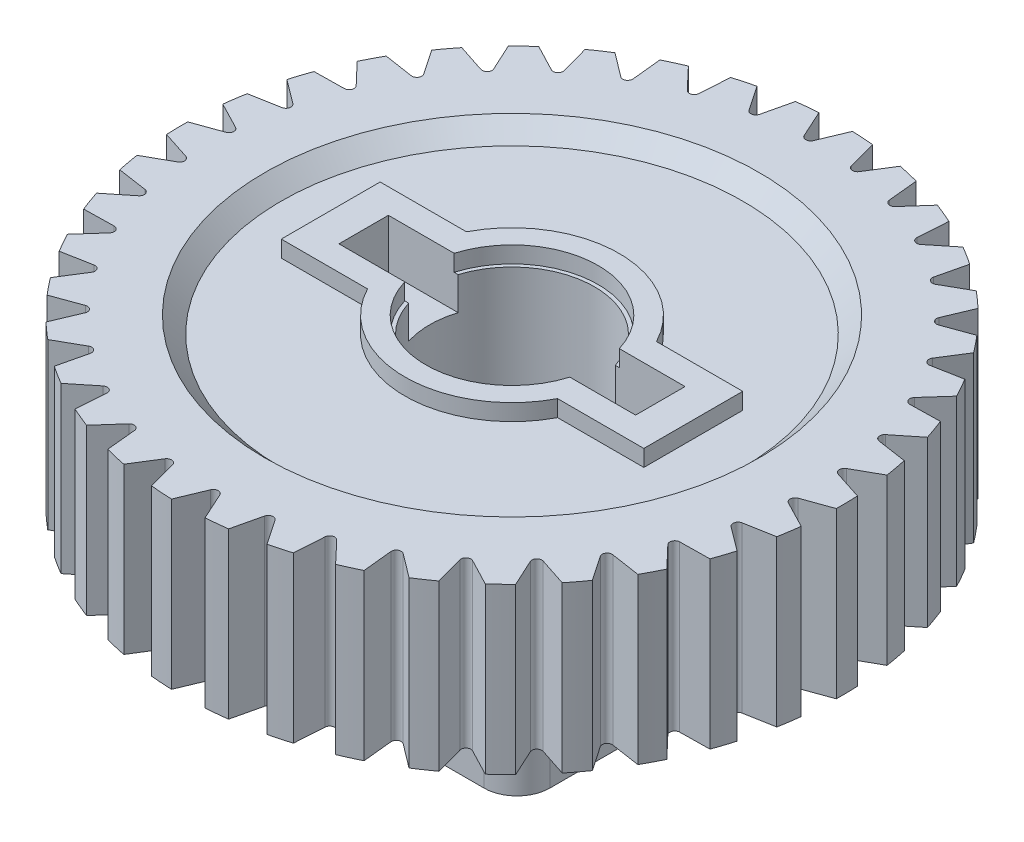
SolidWorks part; units mm, degrees
material "PBT General Purpose"
ref_plane "Front Plane" through (0, 0, 0) normal (0, 0, 1) x (1, 0, 0)
ref_plane "Top Plane" through (0, 0, 0) normal (0, 1, 0) x (1, 0, 0)
ref_plane "Right Plane" through (0, 0, 0) normal (1, 0, 0) x (0, 0, -1)
sketch "Sketch1" plane through (0, 0, 0) normal (0, 1, 0) x (1, 0, 0)
  line L0 (0, 0) -> (12.8047, 15.3636) construction
  line L1 (0, 0) -> (11.2062, 16.5657) construction
  line L2 (11.2062, 16.5657) -> (10.6283, 14.1334)
  line L3 (10.6283, 14.1334) -> (12.8047, 15.3636)
  circle A0 centre (0, 0) radius 20
  dimension "D1" = 40
  dimension "D2" = 2
  dimension "D3" = 2.5
extrude "Boss-Extrude1" add sketch "Sketch1" along normal blind 10 contours L2 A0 L3 region at (-0.0214, 0, 0.0285)
fillet "Fillet1" radius 0.3 1 edges at (10.6283, 5, -14.1334)
ref_axis "Axis1" through (0, 10, 0) along (0, -1, 0)
pattern_circular "CirPattern1" count 38 over 360 about axis through (0, 10, 0) along (0, -1, 0) of face at (12.0157, 5, -14.9176) of face at (10.9529, 5, -14.565) of face at (10.9967, 5, -15.6839)
sketch "Sketch2" plane through (0, 10, 0) normal (0, 1, 0) x (1, 0, 0)
  circle A0 centre (0, 0) radius 5
  dimension "D1" = 10
extrude "Cut-Extrude1" cut sketch "Sketch2" against normal blind 10
sketch "Sketch3" plane through (0, 10, 0) normal (0, 1, 0) x (1, 0, 0)
  circle A0 centre (0, 0) radius 14
  dimension "D1" = 28
extrude "Cut-Extrude2" cut sketch "Sketch3" against normal blind 1
chamfer "Chamfer1" distance 1 angle 45 1 edges at (0, 10, 14)
sketch "Sketch4" plane through (0, 9, 0) normal (0, 1, 0) x (1, 0, 0)
  line L1 (-11, 3) -> (11, 3)
  line L2 (-11, 3) -> (-11, -3)
  line L3 (-11, -3) -> (11, -3)
  line L4 (11, 3) -> (11, -3)
  line L5 (-11, 3) -> (11, -3) construction
  line L6 (-11, -3) -> (11, 3) construction
  line L7 (-9, 1.5) -> (9, 1.5)
  line L8 (-9, 1.5) -> (-9, -1.5)
  line L9 (-9, -1.5) -> (9, -1.5)
  line L10 (9, 1.5) -> (9, -1.5)
  line L11 (-9, 1.5) -> (9, -1.5) construction
  line L12 (-9, -1.5) -> (9, 1.5) construction
  circle A0 centre (0, 0) radius 5.2289
  circle A1 centre (0, 0) radius 6.5
  point P0 (0, 0)
  point P6 (0, 0)
  dimension "D5" = 13
  dimension "D1" = 22
  dimension "D2" = 6
  dimension "D3" = 2
  dimension "D4" = 1.5
extrude "Boss-Extrude2" add sketch "Sketch4" along normal blind 1 contours L1 A1 A0 | L1 A1 L7 A0 | A1 L1 L2 L3 L9 L8 L7 | L9 A1 L3 A0 | L3 A1 A0 | L3 A1 L9 A0 | A1 L3 L4 L1 L7 L10 L9 | L7 A1 L1 A0 region at (-8.3831, 9, -2.9204) region at (0, 9, -6.3795) region at (-5.3816, 9, -2.2649) region at (5.3816, 9, -2.2649) region at (8.3831, 9, -2.9204) region at (-5.3816, 9, 2.2649) region at (-5.0245, 9, 3.1205) region at (5.3816, 9, 2.2649)
sketch "Sketch5" plane through (0, 9, 0) normal (0, 1, 0) x (1, 0, 0)
  line L1 (-9, 1.5) -> (9, 1.5)
  line L2 (-9, 1.5) -> (-9, -1.5)
  line L3 (-9, -1.5) -> (9, -1.5)
  line L4 (9, 1.5) -> (9, -1.5)
  line L5 (-9, 1.5) -> (9, -1.5) construction
  line L6 (-9, -1.5) -> (9, 1.5) construction
  point P0 (0, 0)
extrude "Cut-Extrude4" cut sketch "Sketch5" against normal blind 2
sketch "Sketch6" plane through (0, 0, 0) normal (0, -1, 0) x (1, 0, 0)
  circle A0 centre (0, 0) radius 15
  dimension "D1" = 30
extrude "Cut-Extrude5" cut sketch "Sketch6" against normal blind 1
chamfer "Chamfer2" distance 1 angle 45 1 edges at (0, 0, -15)
sketch "Sketch7" plane through (0, 1, 0) normal (0, -1, 0) x (1, 0, 0)
  line L1 (-7, 6.6987) -> (7, 6.6987)
  line L2 (-7, 6.6987) -> (-7, -6.6987)
  line L3 (-7, -6.6987) -> (7, -6.6987)
  line L4 (7, 6.6987) -> (7, -6.6987)
  line L5 (-7, 6.6987) -> (7, -6.6987) construction
  line L6 (-7, -6.6987) -> (7, 6.6987) construction
  point P0 (0, 0)
  dimension "D1" = 7
extrude "Boss-Extrude3" add sketch "Sketch7" along normal blind 10
sketch "Sketch8" plane through (0, -9, 0) normal (0, -1, 0) x (1, 0, 0)
  circle A0 centre (0, 0) radius 5
  dimension "D1" = 10
extrude "Cut-Extrude6" cut sketch "Sketch8" against normal blind 10
fillet "Fillet2" radius 2 4 edges at (-7, -4, -6.6987) (7, -4, -6.6987) (7, -4, 6.6987) (-7, -4, 6.6987)
equation "\"w\"=0.3"
